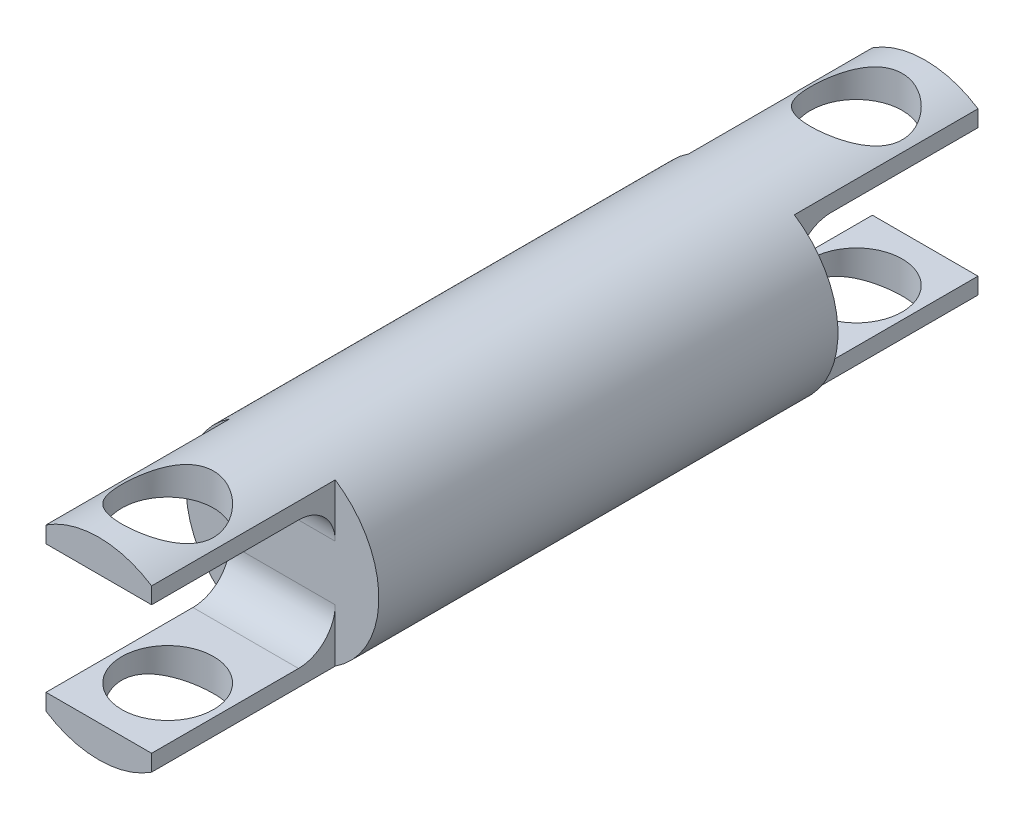
SolidWorks part; units mm, degrees
ref_plane "Płaszczyzna przednia" through (0, 0, 0) normal (0, 0, 1) x (1, 0, 0)
ref_plane "Płaszczyzna górna" through (0, 0, 0) normal (0, 1, 0) x (1, 0, 0)
ref_plane "Płaszczyzna prawa" through (0, 0, 0) normal (1, 0, 0) x (0, 0, -1)
sketch "Szkic1" plane through (0, 0, 0) normal (0, 0, 1) x (1, 0, 0)
  circle A0 centre (0, 0) radius 21
  dimension "D1" = 42
extrude "Dodanie-wyciągnięcie1" add sketch "Szkic1" along normal blind 50 contours A0
sketch "Szkic6" plane through (0, 0, 50) normal (0, 0, 1) x (1, 0, 0)
  line L0 (-11.5, 17.5713) -> (-11.5, 14)
  line L1 (-11.5, 14) -> (11.5, 14)
  line L2 (11.5, 14) -> (11.5, 17.5713)
  line L3 (0, 0) -> (13.4968, 0) construction
  line L4 (11.5, -14) -> (11.5, -17.5713)
  line L5 (-11.5, -14) -> (11.5, -14)
  line L6 (-11.5, -17.5713) -> (-11.5, -14)
  circle A0 centre (0, 0) radius 21 construction
  arc A1 (-11.5, -17.5713) -> (11.5, -17.5713) centre (0, 0) ccw
  arc A2 (11.5, 17.5713) -> (-11.5, 17.5713) centre (0, 0) ccw
  dimension "D1" = 14
  dimension "D2" = 11.5
  dimension "D3" = 11.5
extrude "Dodanie-wyciągnięcie4" add sketch "Szkic6" along normal blind 40
sketch "Szkic7" plane through (0, -14, 0) normal (0, 1, 0) x (1, 0, 0)
  line L0 (11.5, -90) -> (-11.5, -90) construction
  line L1 (11.5, -50) -> (-11.5, -50) construction
  circle A0 centre (0, -75) radius 10
  point P7 (0, -50)
  dimension "D1" = 20
  dimension "D2" = 15
extrude "Wytnij-wyciągnięcie1" cut sketch "Szkic7" along normal blind 40 and the other way up to next
fillet "Zaokrąglenie1" radius 8 2 edges at (0, -14, 50) (0, 14, 50)
mirror "Lustro2" about plane through (0, 0, 0) normal (0, 0, 1) of "Dodanie-wyciągnięcie1", "Zaokrąglenie1", "Wytnij-wyciągnięcie1", "Dodanie-wyciągnięcie4"
